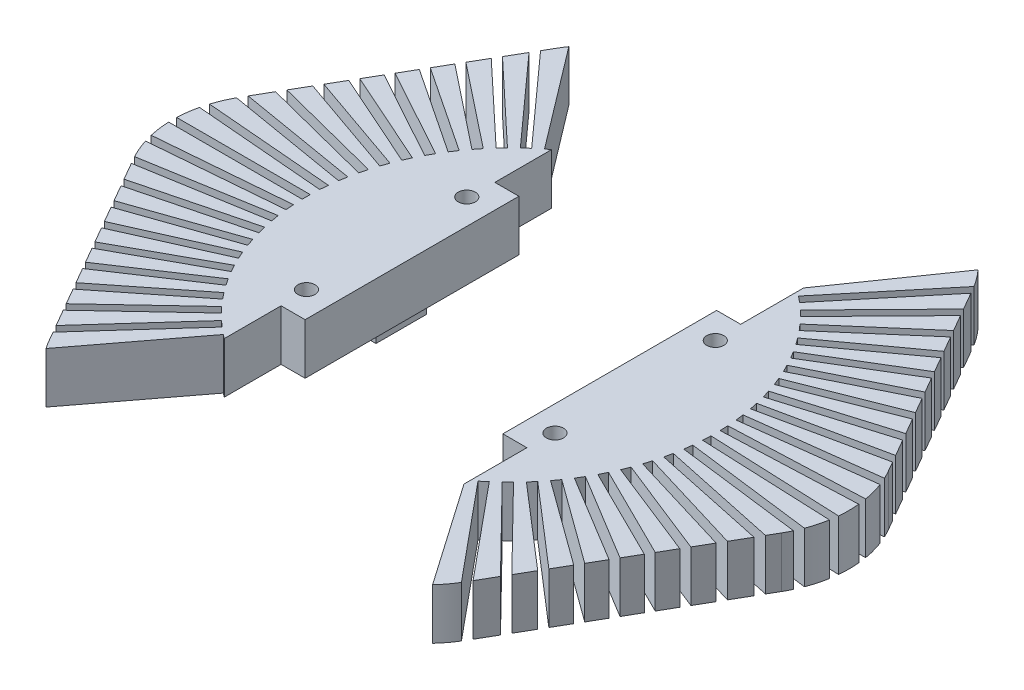
SolidWorks part; units mm, degrees
ref_plane "Front Plane" through (0, 0, 0) normal (0, 0, 1) x (1, 0, 0)
ref_plane "Top Plane" through (0, 0, 0) normal (0, 1, 0) x (1, 0, 0)
ref_plane "Right Plane" through (0, 0, 0) normal (1, 0, 0) x (0, 0, -1)
sketch "Sketch1" plane through (0, 0, 0) normal (0, 1, 0) x (1, 0, 0)
  line L1 (60.6218, 10) -> (38.9711, 47.5)
  line L2 (21.6506, 57.5) -> (-21.6506, 57.5)
  line L3 (-38.9711, 47.5) -> (-60.6218, 10)
  line L4 (-60.6218, -10) -> (-38.9711, -47.5)
  line L5 (-21.6506, -57.5) -> (21.6506, -57.5)
  line L6 (38.9711, -47.5) -> (60.6218, -10)
  circle A0 centre (0, 0) radius 57.5 construction
  arc A1 (-21.6506, -57.5) -> (-38.9711, -47.5) centre (-21.6506, -37.5) cw
  arc A2 (21.6506, -57.5) -> (38.9711, -47.5) centre (21.6506, -37.5) ccw
  arc A3 (60.6218, -10) -> (60.6218, 10) centre (43.3013, 0) ccw
  arc A4 (38.9711, 47.5) -> (21.6506, 57.5) centre (21.6506, 37.5) ccw
  arc A5 (-21.6506, 57.5) -> (-38.9711, 47.5) centre (-21.6506, 37.5) ccw
  arc A6 (-60.6218, -10) -> (-60.6218, 10) centre (-43.3013, 0) cw
  dimension "D1" = 115
  dimension "D2" = 20
extrude "Boss-Extrude2" add sketch "Sketch1" along normal blind 77.5
sketch "Sketch6" plane through (0, 77.5, 0) normal (0, 1, 0) x (1, 0, 0)
  circle A0 centre (0, 0) radius 13
extrude "Cut-Extrude1" cut sketch "Sketch6" against normal up to surface (77.5 mm away) up to face at (0, 0, 0)
sketch "Sketch7" plane through (0, 0, 0) normal (0, 0, 1) x (1, 0, 0)
  line L0 (0, 77.5) -> (0, 0) construction
  line L1 (-21.6506, 77.5) -> (21.6506, 77.5) construction
  line L2 (0, 77.5) -> (13, 77.5) construction
  line L3 (13, 77.5) -> (13, 60)
  line L4 (13, 77.5) -> (30.5, 77.5)
  line L5 (38.9711, 77.5) -> (21.6506, 77.5) construction
  line L6 (13, 0) -> (63.3013, 0) construction
  line L7 (38.9711, 0) -> (38.9711, 77.5) construction
  line L8 (64.9423, 77.5) -> (47.4423, 77.5)
  line L9 (64.9423, 77.5) -> (64.9423, 60)
  line L10 (13, 77.5) -> (-13, 77.5) construction
  line L11 (13, 77.5) -> (18.5176, 71.4317) construction
  spline S0 degree 2 poles (13, 60) (14.0037, 72.8919) (30.5, 77.5) knots 0 0 0 1 1 1
  spline S1 degree 2 poles (64.9423, 60) (63.9386, 72.8919) (47.4423, 77.5) knots 0 0 0 1 1 1
  dimension "D1" = 13
  dimension "D2" = 17.5
  dimension "D3" = 17.5
  dimension "D4" = 8.2017
revolve "Cut-Revolve1" cut sketch "Sketch7" angle 360 about L0
ref_plane "Plane1" through (0, 38.75, 0) normal (0, 1, 0) x (1, 0, 0)
sketch "Sketch8" plane through (0, 0, 0) normal (0, 0, 1) x (1, 0, 0)
  line L0 (-63.3013, 77.5) -> (-63.3013, 0)
  line L1 (-13.3013, 5) -> (-38.3013, 5) construction
  line L2 (-38.3013, 5) -> (-38.3013, 0)
  line L3 (-63.3013, 0) -> (-38.3013, 0)
  line L4 (-13.3013, 0) -> (-13.3013, 5) construction
  line L5 (-38.3013, 5) -> (-38.3013, 72.5)
  line L6 (63.25, 38.75) -> (-63.25, 38.75) construction
  line L7 (-63.3013, 38.75) -> (-38.3013, 38.75) construction
  line L8 (-13.3013, 77.5) -> (-13.3013, 72.5)
  line L9 (-63.3013, 77.5) -> (-13.3013, 77.5)
  line L10 (-13.3013, 72.5) -> (-38.3013, 72.5)
  line L11 (-38.3013, 0) -> (-13.3013, 0) construction
  point P3 (-66.188, 24)
  dimension "D1" = 50
  dimension "D2" = 50
  dimension "D3" = 5
  dimension "D4" = 25
extrude "Cut-Extrude2" cut sketch "Sketch8" against normal blind 0.75 and the other way blind 0.75
pattern_circular "CirPattern1" count 75 over 360 about axis through (0, 0, 0) along (0, 1, 0) of "Cut-Extrude2"
sketch "Sketch9" plane through (0, 77.5, 0) normal (0, 1, 0) x (1, 0, 0)
  line L1 (51.9615, 0) -> (25.9808, 45)
  line L2 (25.9808, 45) -> (-25.9808, 45)
  line L3 (-25.9808, 45) -> (-51.9615, 0)
  line L4 (-51.9615, 0) -> (-25.9808, -45)
  line L5 (-25.9808, -45) -> (25.9808, -45)
  line L6 (25.9808, -45) -> (51.9615, 0)
  circle A0 centre (0, 0) radius 45 construction
  dimension "D1" = 90
extrude "Cut-Extrude3" cut sketch "Sketch9" against normal blind 63 flip side to cut
sketch "Sketch12" plane through (0, 77.5, 0) normal (0, 1, 0) x (1, 0, 0)
  line L1 (78.4316, 67.013) -> (-78.4316, 67.013)
  line L2 (78.4316, 67.013) -> (78.4316, -67.013)
  line L3 (78.4316, -67.013) -> (-78.4316, -67.013)
  line L4 (-78.4316, 67.013) -> (-78.4316, -67.013)
  line L5 (78.4316, 67.013) -> (-78.4316, -67.013) construction
  line L6 (78.4316, -67.013) -> (-78.4316, 67.013) construction
  point P0 (0, 0)
extrude "Cut-Extrude7" cut sketch "Sketch12" against normal blind 68
sketch "Sketch11" plane through (0, 0, 0) normal (0, -1, 0) x (1, 0, 0)
  line L0 (-18.5, 0) -> (18.5, 0) construction
  line L5 (-23, 20) -> (-18.5, 20)
  line L6 (23, 67.6503) -> (-23, 67.6503)
  line L7 (23, 67.6503) -> (23, 20)
  line L8 (23, -67.6503) -> (-23, -67.6503)
  line L9 (-23, 67.6503) -> (-23, 20)
  line L10 (23, 67.6503) -> (-23, -67.6503) construction
  line L11 (23, -67.6503) -> (-23, 67.6503) construction
  line L12 (18.5, 20) -> (6.7997, 20) construction
  line L13 (18.5, 20) -> (18.5, -20)
  line L14 (-6.7997, -20) -> (-18.5, -20) construction
  line L15 (-18.5, 20) -> (-18.5, -20)
  line L16 (18.5, 20) -> (-18.5, -20) construction
  line L17 (18.5, -20) -> (-18.5, 20) construction
  line L18 (-23, -20) -> (-18.5, -20)
  line L19 (-23, 20) -> (-23, 0) construction
  line L20 (-23, -20) -> (-23, -67.6503)
  line L21 (-23, 0) -> (-18.5, 0) construction
  line L22 (-23, 0) -> (-23, -20) construction
  line L23 (23, 20) -> (23, -20) construction
  line L24 (23, -20) -> (23, -67.6503)
  line L25 (-18.5, 20) -> (-6.7997, 20) construction
  line L26 (18.5, 20) -> (23, 20)
  line L27 (-6.7997, 20) -> (-18.5, 20) construction
  line L28 (6.7997, 20) -> (-6.7997, 20) construction
  line L29 (-6.7997, 20) -> (6.7997, 20) construction
  line L30 (6.7997, 20) -> (18.5, 20) construction
  line L31 (6.7997, -20) -> (18.5, -20) construction
  line L32 (18.5, -20) -> (23, -20)
  line L33 (18.5, -20) -> (6.7997, -20) construction
  line L34 (-6.7997, -20) -> (6.7997, -20) construction
  line L35 (6.7997, -20) -> (-6.7997, -20) construction
  line L36 (-18.5, -20) -> (-6.7997, -20) construction
  point P0 (0, 0)
  point P7 (0, 0)
  point P10 (0, 0)
  dimension "D1" = 46
  dimension "D2" = 37
  dimension "D3" = 40
extrude "Cut-Extrude9" cut sketch "Sketch11" against normal blind 60
sketch "Sketch14" plane through (0, 0, 0) normal (0, -1, 0) x (1, 0, 0)
  line L0 (-23.25, 0) -> (0, 0) construction
  line L1 (0, 0) -> (0, 14.4946) construction
  line L2 (20.5, -4.75) -> (26, 4.75) construction
  line L3 (-20.5, 4.75) -> (-26, 4.75)
  line L4 (-20.5, 4.75) -> (-20.5, -4.75)
  line L5 (-20.5, -4.75) -> (-26, -4.75)
  line L6 (-26, 4.75) -> (-26, -4.75)
  line L7 (-20.5, 4.75) -> (-26, -4.75) construction
  line L8 (-20.5, -4.75) -> (-26, 4.75) construction
  line L9 (20.5, 4.75) -> (26, -4.75) construction
  line L10 (26, 4.75) -> (26, -4.75)
  line L11 (20.5, -4.75) -> (26, -4.75)
  line L12 (20.5, 4.75) -> (20.5, -4.75)
  line L13 (20.5, 4.75) -> (26, 4.75)
  dimension "D1" = 5.5
  dimension "D2" = 23.25
  dimension "D3" = 9.5
extrude "Boss-Extrude3" add sketch "Sketch14" along normal blind 3
sketch "Sketch15" plane through (0, 0, 0) normal (0, -1, 0) x (1, 0, 0)
  circle A0 centre (-23.25, 15) radius 1.6
  circle A1 centre (-23.25, -15) radius 1.6
  circle A2 centre (23.25, -15) radius 1.6
  circle A3 centre (23.25, 15) radius 1.6
  dimension "D1" = 3.2
extrude "Cut-Extrude10" cut sketch "Sketch15" against normal up to surface (9.5 mm away) up to face at (41.3234, 9.5, 0)
